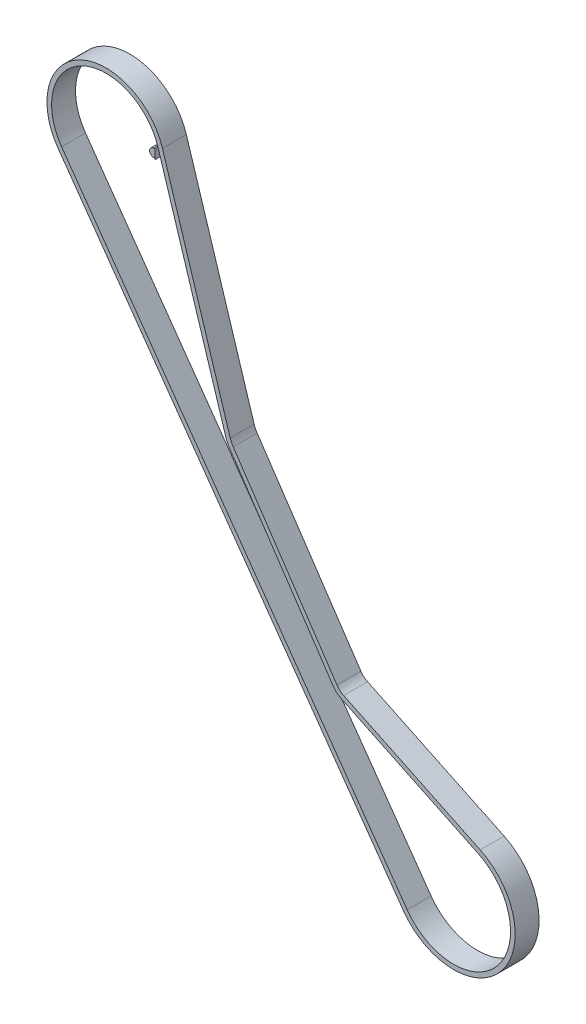
SolidWorks part; units mm, degrees
ref_plane "Front Plane" through (0, 0, 0) normal (0, 0, 1) x (1, 0, 0)
ref_plane "Top Plane" through (0, 0, 0) normal (0, 1, 0) x (1, 0, 0)
ref_plane "Right Plane" through (0, 0, 0) normal (1, 0, 0) x (0, 0, -1)
sketch "Sketch2" plane through (0, 0, 0) normal (0, 0, 1) x (1, 0, 0)
  line L0 (0, 0) -> (1, 0) construction
  line L1 (0, 0) -> (0, 1) construction
  line L13 (104.4612, -212.6042) -> (-25.5754, -28.9888)
  line L18 (12.2439, -10.2735) -> (37.7495, -91.9017)
  line L19 (38.979, -94.4644) -> (78.0026, -152.5172)
  line L20 (80.8744, -155.0002) -> (132.2744, -179.6332)
  arc A4 (132.2744, -179.6332) -> (104.4612, -212.6042) centre (122.6448, -199.7266) cw
  arc A7 (-25.5754, -28.9888) -> (12.2439, -10.2735) centre (-8.144, -16.6439) cw
  arc A8 (78.0026, -152.5172) -> (80.8744, -155.0002) centre (83.9947, -148.4893) ccw
  arc A10 (37.7495, -91.9017) -> (38.979, -94.4644) centre (47.1703, -88.9581) ccw
extrude "Extrude-Thin1" add sketch "Sketch2" along normal blind 9 thin thin type two direction wall 0.87 second wall 0.87
sketch "Sketch3" plane through (0, 0, 0) normal (0, 0, -1) x (-1, 0, 0)
  line L0 (-10.355, -15.0922) -> (-10.2744, -11.1887)
  line L1 (24.8654, -28.486) -> (-105.1712, -212.1014) construction
  line L3 (-10.355, -15.0922) -> (-10.334, -14.0773) construction
  arc A0 (-9.893, -14.6722) -> (-9.8302, -11.6273) centre (-9.7795, -13.1515) ccw
  arc A1 (-10.355, -15.0922) -> (-9.893, -14.6722) centre (-9.9251, -15.101) cw
  arc A2 (-10.2744, -11.1887) -> (-9.8302, -11.6273) centre (-9.8445, -11.1975) ccw
  point P2 (-8.2545, -13.1515)
  dimension "D1" = 3.05
  dimension "D3" = 0.43
  dimension "D2" = 2.06
extrude "Boss-Extrude1" add sketch "Sketch3" against normal up to surface (9 mm away) up to face at (58.9948, -114.8979, 9)
pattern_curve "CrvPattern1" rebuild error yes driven by "Sketch2" parameters "D1"=119, "D3"=5, "D2"=1, "D4"=50
